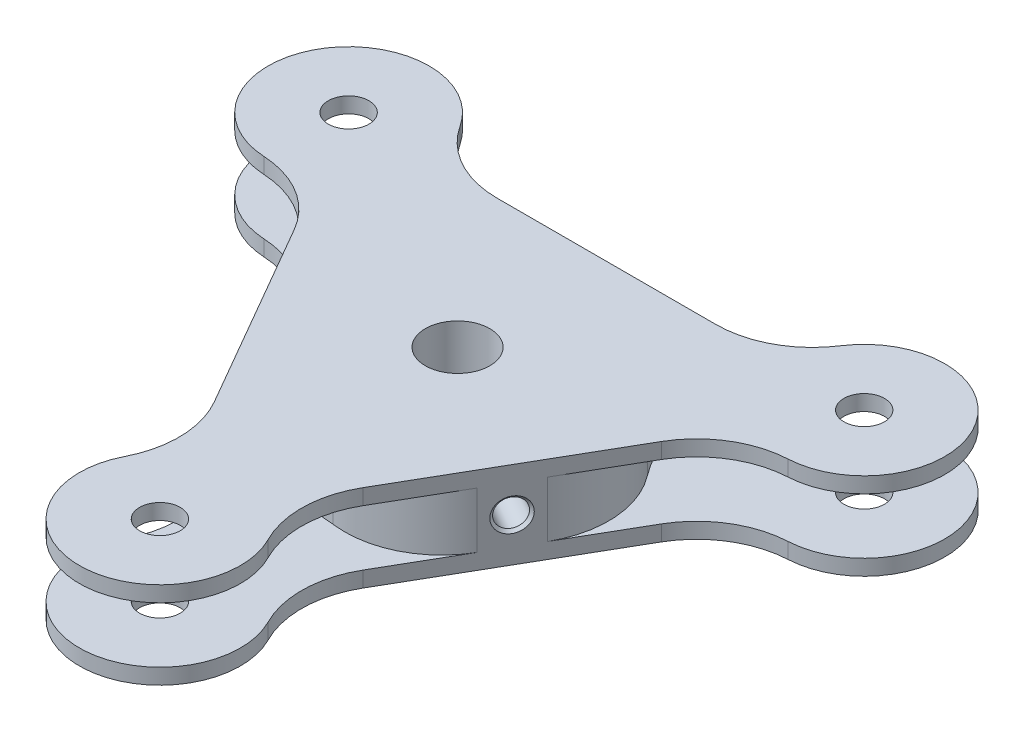
SolidWorks part; units mm, degrees
ref_plane "Plan de face" through (0, 0, 0) normal (0, 0, 1) x (1, 0, 0)
ref_plane "Plan de dessus" through (0, 0, 0) normal (0, 1, 0) x (1, 0, 0)
ref_plane "Plan de droite" through (0, 0, 0) normal (1, 0, 0) x (0, 0, -1)
sketch "Esquisse1" plane through (0, 0, 0) normal (0, 1, 0) x (1, 0, 0)
  line L3 (20, -11.547) -> (-40, 23.094) construction
  line L6 (-20, -11.547) -> (40, 23.094) construction
  line L16 (40, 23.094) -> (0, -46.188)
  line L17 (0, -46.188) -> (-40, 23.094)
  line L19 (-40, 23.094) -> (40, 23.094)
  circle A6 centre (0, 0) radius 5
  circle A7 centre (40, 23.094) radius 12.5
  circle A9 centre (0, -46.188) radius 12.5
  circle A10 centre (-40, 23.094) radius 12.5
  point P11 (0, 0)
  point P12 (5.3523, 54.348)
  point P36 (0, 50)
  point P38 (0, 50)
  point P40 (0, 50)
  point P41 (0, 50)
  dimension "D2" = 5.3523
  dimension "D3" = 80
  dimension "D5" = 25
  dimension "D1" = 80
  dimension "D6" = 25
  dimension "D8" = 10
  dimension "D7" = 25
  dimension "D4" = 80
extrude "Boss.-Extru.1" add sketch "Esquisse1" along normal mid plane 13.5 contours A10 L17 A9 L16 A7 L19 A6 | L19 A10 L17 | L16 A7 L19 | L19 A7 L16 | L17 A10 L19 | L17 A9 L16 | L16 A9 L17 region at (41.3783, 0, -23.8898) region at (33.1084, 0, -19.1151) region at (19.2267, 0, 11.1005) region at (0, 0, 47.7796) region at (0, 0, 38.2303) region at (-33.1084, 0, -19.1151) region at (-41.3783, 0, -23.8898)
sketch "Esquisse7" plane through (0, 0, 0) normal (0, 1, 0) x (1, 0, 0)
  circle A9 centre (-40, 23.094) radius 24
  circle A10 centre (0, -46.188) radius 24
  circle A11 centre (40, 23.094) radius 24
  dimension "D1" = 48
  dimension "D2" = 48
  dimension "D3" = 48
extrude "Enlèv. mat.-Extru.1" cut sketch "Esquisse7" against normal mid plane 8.65
fillet "Congé6" radius 15 6 edges at (28, 0, -2.3094) (12, 0, 25.4034) (-28, 0, -2.3094) (-12, 0, 25.4034) (16, 0, -23.094) (-16, 0, -23.094)
sketch "Esquisse22" plane through (20, 0, 11.547) normal (0.866, 0, 0.5) x (0.5, 0, -0.866)
  point P0 (0, 0)
  point P3 (0, 0)
hole_wizard "Trou taraudé M51" positions "Esquisse22" profile "Esquisse23" tap size "M5" standard "ISO" end condition up to next
sketch "Esquisse23" plane through (20, 0, 11.547) normal (0, 1, 0) x (0.5, 0, -0.866)
  line L0 (0, 0) -> (0, 45.282)
  line L1 (0, 45.282) -> (2.1, 45.282)
  line L2 (2.1, 45.282) -> (2.1, 0.425)
  line L3 (2.1, 0.425) -> (2.525, 0)
  line L5 (2.525, 0) -> (0, 0)
  line L6 (-2.1, 0.425) -> (-2.525, 0) construction
  line L11 (0, -6.35) -> (0, 107.95) construction
  dimension "Diamètre du trou pour taraudage jusqu'au prochain" = 4.2
  dimension "Profondeur du trou pour taraudage jusqu'au prochain" = 45.282
  dimension "Diamètre du fraisage entrant" = 5.05
  dimension "Angle du fraisage entrant" = 90
cosmetic thread "Filetage de perçage2" parameters "D2"=5
cosmetic thread "Filetage de perçage3" parameters "D2"=5.85
fillet "Congé7" radius 15 12 edges at (27.5, 5.5375, -23.094) (27.5, -5.5375, -23.094) (-27.5, -5.5375, -23.094) (-27.5, 5.5375, -23.094) (-33.75, 5.5375, -12.2687) (-33.75, -5.5375, -12.2687) (-6.25, -5.5375, 35.3627) (-6.25, 5.5375, 35.3627) (6.25, -5.5375, 35.3627) (6.25, 5.5375, 35.3627) (33.75, 5.5375, -12.2687) (33.75, -5.5375, -12.2687)
sketch "Esquisse25" plane through (0, 6.75, 0) normal (0, 1, 0) x (1, 0, 0)
  circle A2 centre (-40, 23.094) radius 3.15
  circle A5 centre (40, 23.094) radius 3.15
  circle A6 centre (0, -46.188) radius 3.15
  dimension "D1" = 6.3
  dimension "D4" = 6.3
  dimension "D5" = 6.3
  dimension "D2" = 40
  dimension "D3" = 23.094
  dimension "D6" = 46.188
  dimension "D7" = 23.094
  dimension "D8" = 40
extrude "Enlèv. mat.-Extru.2" cut sketch "Esquisse25" against normal through all
